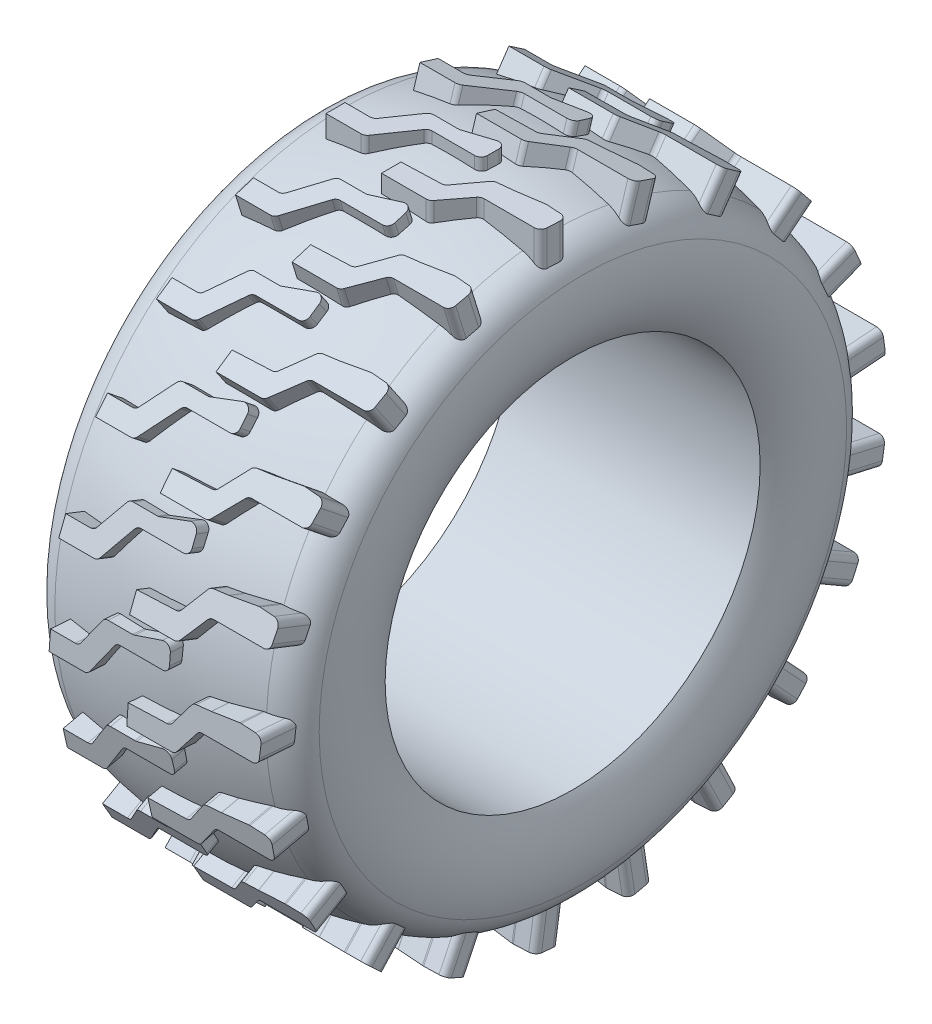
SolidWorks part; units mm, degrees
ref_plane "Front Plane" through (0, 0, 0) normal (0, 0, 1) x (1, 0, 0)
ref_plane "Top Plane" through (0, 0, 0) normal (0, 1, 0) x (1, 0, 0)
ref_plane "Right Plane" through (0, 0, 0) normal (1, 0, 0) x (0, 0, -1)
sketch "Sketch2" plane through (0, 0, 0) normal (0, 0, 1) x (1, 0, 0)
  line L0 (-383.8953, 0) -> (0, 0) construction
  line L1 (0, 0) -> (0, 290) construction
  line L5 (190.2474, 290) -> (-189.7526, 290)
  line L7 (190.2474, 440) -> (-189.7526, 290) construction
  line L8 (190.2474, 290) -> (-190.7435, 440) construction
  arc A0 (-190.7435, 440) -> (190.2474, 440) centre (-0.2481, -233.5811) cw
  arc A1 (-190.7435, 440) -> (-189.7526, 290) centre (-79.2065, 365.7336) ccw
  arc A2 (190.2474, 440) -> (190.2474, 290) centre (79.2024, 365) cw
  point P3 (0, 364.9023)
  point P12 (-189.7526, 510)
  dimension "D4" = 134
  dimension "D5" = 134
  dimension "D6" = 700
  dimension "D1" = 150
  dimension "D2" = 380
  dimension "D3" = 290
revolve "Revolve1" add sketch "Sketch2" angle 360 about L0
fillet "Fillet1" radius 60 2 edges at (-190.7435, 0, 440) (190.2474, 0, 440)
ref_plane "Plane1" through (0, 410, 0) normal (0, 1, 0) x (1, 0, 0)
sketch "Sketch3" plane through (0, 410, 0) normal (0, 1, 0) x (1, 0, 0)
  line L0 (0, 213.0271) -> (0, -160.7238) construction
  line L1 (48.6269, 27.3512) -> (48.6269, 10)
  line L2 (38.6269, 0) -> (-26.9482, 0)
  line L3 (-35.1651, -4.3006) -> (-69.9997, -54.5223)
  line L4 (-78.2166, -58.8229) -> (-132.401, -58.8229)
  line L5 (-132.401, -58.8229) -> (-132.401, -29.4114)
  line L6 (-132.401, -29.4114) -> (-94.0615, -29.4114)
  line L7 (-85.8446, -25.1108) -> (-55.5654, 18.5432)
  line L8 (-47.3485, 22.8438) -> (-9.5466, 22.8438)
  line L9 (-6.4802, 23.3256) -> (35.5604, 36.8695)
  line L21 (-9.5466, -65.6706) -> (-9.5466, -95.7955)
  line L22 (-9.5466, -95.7955) -> (59.4827, -95.7955)
  line L23 (67.4202, -91.8781) -> (96.0492, -54.5186)
  line L24 (103.9866, -50.6012) -> (181.4181, -50.6012)
  line L25 (191.3999, -41.2036) -> (192.5591, -21.9962)
  line L26 (183.1797, -11.412) -> (160.8181, -10.0624)
  line L27 (158.7605, -10.1507) -> (115.5699, -16.5034)
  line L28 (-9.5466, -65.6706) -> (50.439, -63.5819)
  line L29 (58.1347, -59.5292) -> (85.1463, -22.9589)
  line L30 (92.1529, -18.9541) -> (115.1518, -16.5559)
  arc A4 (-9.5466, 22.8438) -> (-6.4802, 23.3256) centre (-9.5466, 32.8438) ccw
  arc A8 (-94.0615, -29.4114) -> (-85.8446, -25.1108) centre (-94.0615, -19.4114) ccw
  arc A9 (-69.9997, -54.5223) -> (-78.2166, -58.8229) centre (-78.2166, -48.8229) cw
  arc A10 (-55.5654, 18.5432) -> (-47.3485, 22.8438) centre (-47.3485, 12.8438) cw
  arc A11 (-26.9482, 0) -> (-35.1651, -4.3006) centre (-26.9482, -10) ccw
  arc A12 (48.6269, 27.3512) -> (35.5604, 36.8695) centre (38.6269, 27.3512) ccw
  arc A13 (48.6269, 10) -> (38.6269, 0) centre (38.6269, 10) cw
  arc A14 (50.439, -63.5819) -> (58.1347, -59.5292) centre (50.091, -53.5879) ccw
  arc A15 (85.1463, -22.9589) -> (92.1529, -18.9541) centre (93.19, -28.9001) cw
  arc A16 (115.5699, -16.5034) -> (115.1518, -16.5559) centre (114.1147, -6.6098) cw
  arc A17 (160.8181, -10.0624) -> (158.7605, -10.1507) centre (160.2157, -20.0442) ccw
  arc A18 (192.5591, -21.9962) -> (183.1797, -11.412) centre (182.5773, -21.3938) ccw
  arc A19 (181.4181, -50.6012) -> (191.3999, -41.2036) centre (181.4181, -40.6012) ccw
  arc A20 (96.0492, -54.5186) -> (103.9866, -50.6012) centre (103.9866, -60.6012) cw
  arc A21 (59.4827, -95.7955) -> (67.4202, -91.8781) centre (59.4827, -85.7955) ccw
  dimension "D1" = 10
extrude "Boss-Extrude1" add sketch "Sketch3" along normal blind 74
pattern_circular "CirPattern1" count 21 over 360 about axis through (-383.8953, 0, 0) along (-1, 0, 0) of "Boss-Extrude1"
